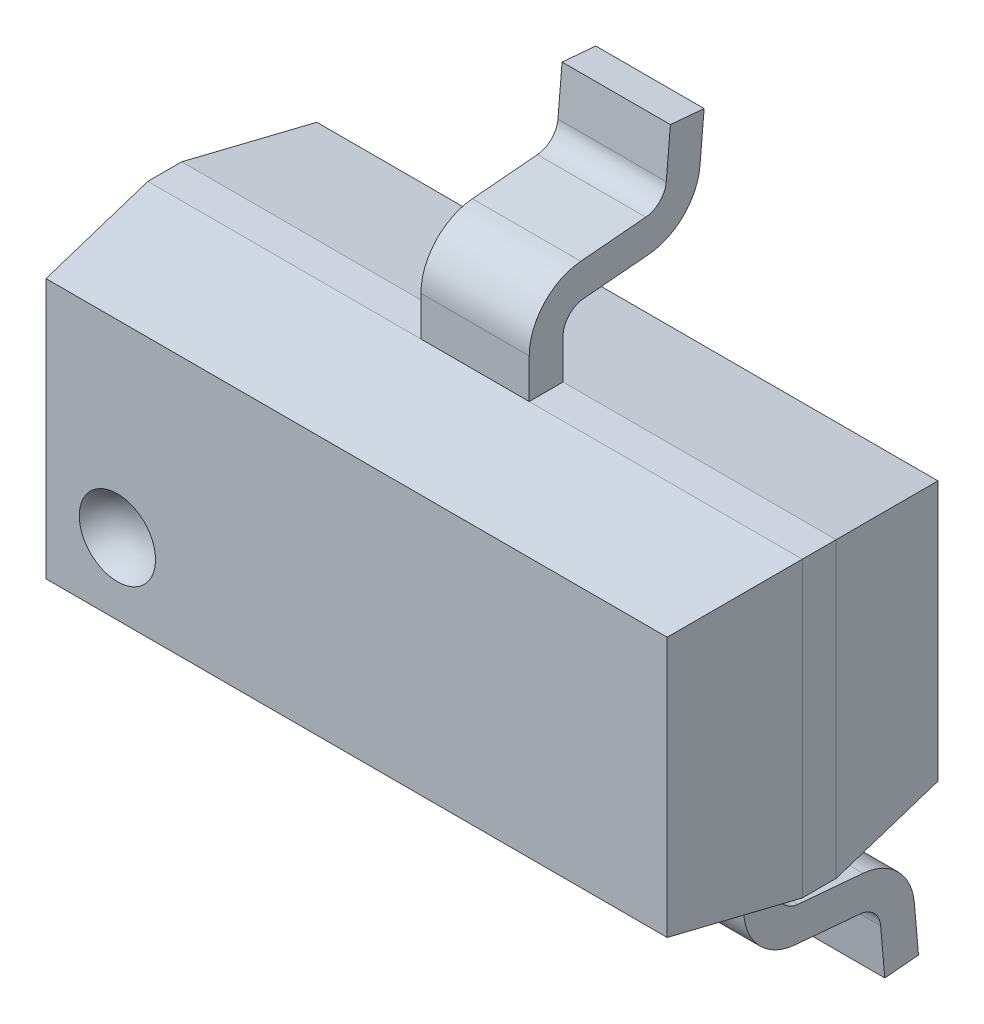
SolidWorks part; units mm, degrees
ref_plane "Top Plane" through (0, 0, 0) normal (0, 0, 1) x (1, 0, 0)
ref_plane "Front Plane" through (0, 0, 0) normal (0, 1, 0) x (1, 0, 0)
ref_plane "Right Plane" through (0, 0, 0) normal (1, 0, 0) x (0, 0, -1)
ref_axis "CenterAxis" through (0, 0, -0.0875) along (0, 0, 1)
ref_plane "Pin1Plane" through (-1.19, 0, 0) normal (1, 0, 0) x (0, 0, -1)
sketch "BodyWxH" plane through (0, 0, 0) normal (1, 0, 0) x (0, 0, -1)
  line L0 (0, 1.54) -> (0, -1.54) construction
  line L1 (-1.3, 0.65) -> (-0.1, 0.65)
  line L2 (-1.3, 0.65) -> (-1.3, -0.65)
  line L3 (-1.3, -0.65) -> (-0.1, -0.65)
  line L4 (-0.1, 0.65) -> (-0.1, -0.65)
  line L6 (-1.3, 0) -> (-0.1, 0) construction
  line L7 (0.0875, 0) -> (-1.8375, 0) construction
  dimension "W" = 1.3
  dimension "SO" = 0.1
  dimension "HMax" = 1.3
extrude "Boss-Body" add sketch "BodyWxH" along normal mid plane 2.9
chamfer "Chamfer1" distance 0.525 angle 8 8 edges at (0, -0.65, 0.1) (1.45, 0, 0.1) (0, 0.65, 0.1) (-1.45, 0, 0.1) (0, 0.65, 1.3) (1.45, 0, 1.3) (0, -0.65, 1.3) (-1.45, 0, 1.3) first distance on face at (0, -0.65, 0.7) first distance on face at (1.45, 0, 0.7) first distance on face at (0, 0.65, 0.7) first distance on face at (-1.45, 0, 0.7)
sketch "LeadCross" plane through (-1.19, 0, 0) normal (1, 0, 0) x (0, 0, -1)
  line L0 (0, -1.3869) -> (-0.1494, -1.4)
  line L1 (-0.1494, -1.4) -> (-0.1678, -1.1903)
  line L2 (-0.2587, -1.0994) -> (-0.5468, -1.0742)
  line L3 (-0.775, -0.8252) -> (-0.775, 0.8252)
  line L4 (-0.5468, 1.0742) -> (-0.2587, 1.0994)
  line L5 (-0.1678, 1.1903) -> (-0.1494, 1.4)
  line L6 (-0.1494, 1.4) -> (0, 1.3869)
  line L7 (0, 1.3869) -> (-0.0183, 1.1773)
  line L8 (-0.2456, 0.95) -> (-0.5337, 0.9248)
  line L9 (-0.625, 0.8252) -> (-0.625, -0.8252)
  line L10 (-0.5337, -0.9248) -> (-0.2456, -0.95)
  line L11 (-0.0183, -1.1773) -> (0, -1.3869)
  line L12 (0, 1.54) -> (0, -1.54) construction
  line L13 (-0.7, 0) -> (0, 0) construction
  line L14 (0.9625, 0) -> (-0.9625, 0) construction
  line L15 (-0.7, 0.6632) -> (-0.7, -0.6632) construction
  arc A0 (-0.0183, 1.1773) -> (-0.2456, 0.95) centre (-0.2674, 1.199) cw
  arc A1 (-0.2587, 1.0994) -> (-0.1678, 1.1903) centre (-0.2674, 1.199) ccw
  arc A2 (-0.2456, -0.95) -> (-0.0183, -1.1773) centre (-0.2674, -1.199) cw
  arc A3 (-0.1678, -1.1903) -> (-0.2587, -1.0994) centre (-0.2674, -1.199) ccw
  arc A4 (-0.625, -0.8252) -> (-0.5337, -0.9248) centre (-0.525, -0.8252) ccw
  arc A5 (-0.5468, -1.0742) -> (-0.775, -0.8252) centre (-0.525, -0.8252) cw
  arc A6 (-0.775, 0.8252) -> (-0.5468, 1.0742) centre (-0.525, 0.8252) cw
  arc A7 (-0.5337, 0.9248) -> (-0.625, 0.8252) centre (-0.525, 0.8252) ccw
  dimension "D2" = 5
  dimension "BendRadius" = 0.1
  dimension "LeadThickness" = 0.15
  dimension "ToeLength" = 0.45
  dimension "D4" = 85
  dimension "MidPlane" = 0.7
  dimension "LeadSpan" = 2.8
extrude "Pins" add sketch "LeadCross" along normal blind 0.48
pattern_linear "PatternLeads" count 3 along (1, 0, 0) of "Pins"
ref_plane "Pin1MarkPlane" through (-1.06, 0, 0) normal (1, 0, 0) x (0, 0, -1)
sketch "Pin1Indent" plane through (-1.06, 0, 0) normal (1, 0, 0) x (0, 0, -1)
  line L0 (-1.3975, -0.065) -> (-1.3975, -0.455) construction
  line L1 (0, 1.54) -> (0, -1.54) construction
  line L2 (-1.3975, -0.26) -> (-1.2025, -0.26) construction
  line L3 (0.9625, 0) -> (-0.9625, 0) construction
  line L4 (-1.3975, -0.065) -> (-1.3975, -0.455)
  arc A1 (-1.3975, -0.455) -> (-1.3975, -0.065) centre (-1.3975, -0.26) ccw
  dimension "CutHeight" = 1.3975
  dimension "CutSize" = 0.39
  dimension "CutOffset" = 0.26
revolve "Cut-Pin1Indent" cut sketch "Pin1Indent" angle 360 mid plane about L4
other "DeleteFace1" face at (0, -1.1366, 0.205) face at (0, -1.2952, 0.1586) face at (0, -1.0868, 0.4027) face at (-0.24, -1.0131, 0.3942) face at (0.24, -1.0131, 0.3942) face at (0, -0.9719, 0.6851) face at (0, -0.7376, 0.775) face at (0, -1.2821, 0.0092) face at (0, -1.043, 0.1113) face at (0, -1.3935, 0.0747) face at (0, -0.8839, 0.589) face at (0, -0.7376, 0.625) face at (0, -0.9374, 0.3897) face at (0.95, 0.9719, 0.6851) face at (0.95, 0.7376, 0.775) face at (0.71, 1.0131, 0.3942) face at (1.19, 1.0131, 0.3942) face at (0.95, 1.0868, 0.4027) face at (0.95, 1.2952, 0.1586) face at (0.95, 1.1366, 0.205) face at (0.95, 1.3935, 0.0747) face at (0.95, 0.8839, 0.589) face at (0.95, 0.9374, 0.3897) face at (0.95, 0.7376, 0.625) face at (0.95, 1.043, 0.1113) face at (0.95, 1.2821, 0.0092) face at (-0.71, 1.0131, 0.3942) face at (-0.95, 0.7376, 0.625) face at (-0.95, 0.8839, 0.589) face at (-0.95, 0.9374, 0.3897) face at (-0.95, 1.043, 0.1113) face at (-0.95, 1.2821, 0.0092) face at (-0.95, 1.3935, 0.0747) face at (-0.95, 1.2952, 0.1586) face at (-0.95, 1.1366, 0.205) face at (-0.95, 1.0868, 0.4027) face at (-0.95, 0.9719, 0.6851) face at (-0.95, 0.7376, 0.775) face at (-1.19, 1.0131, 0.3942) and patch yes
equation "\"D1@Chamfer1\" = (\"HMax@BodyWxH\"-\"SO@BodyWxH\"-\"LeadThickness@LeadCross\")/2"
equation "\"D1@Pin1Plane\" = (\"D1@PatternLeads\"-1)*\"LeadPitch@PatternLeads\"/2+(\"LeadWidth@Pins\"/2) ' 1st pin edge plane"
equation "\"CutSize@Pin1Indent\" = \"W@BodyWxH\"*0.3 ' Dent radius is half this value"
equation "\"CutOffset@Pin1Indent\" = \"W@BodyWxH\"/2-(\"W@BodyWxH\"*0.3) ' Dent distance from the center line"
equation "\"D1@Pin1MarkPlane\" = \"D1@Boss-Body\"/2-(\"W@BodyWxH\"*0.3) ' Pin 1 dent lies along this plane"
equation "\"CutHeight@Pin1Indent\" = \"HMax@BodyWxH\"+(\"CutSize@Pin1Indent\"/4) ' Dent is cut by sphere this high"
equation "\"MidPlane@LeadCross\" = (\"HMax@BodyWxH\"+\"SO@BodyWxH\")/2"
